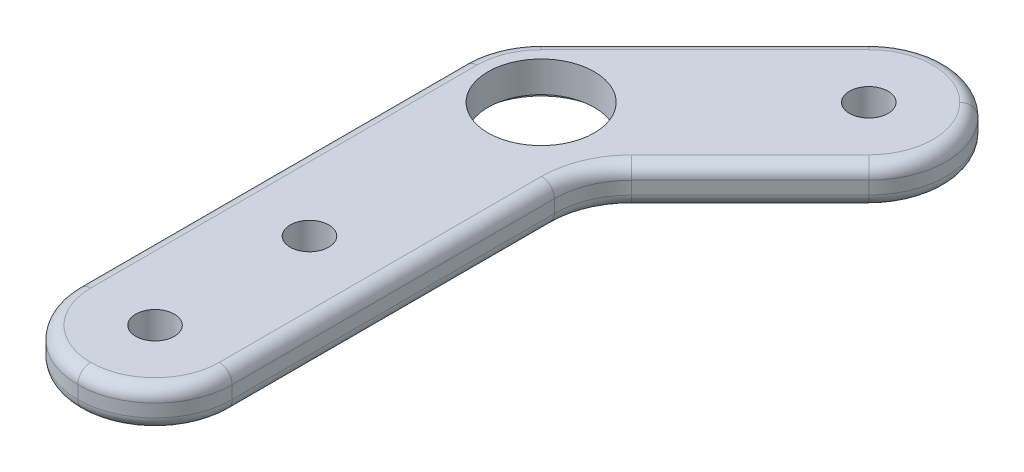
SolidWorks part; units mm, degrees
material "6061 Alloy"
ref_plane "Front Plane" through (0, 0, 0) normal (0, 0, 1) x (1, 0, 0)
ref_plane "Top Plane" through (0, 0, 0) normal (0, 1, 0) x (1, 0, 0)
ref_plane "Right Plane" through (0, 0, 0) normal (1, 0, 0) x (0, 0, -1)
sketch "Sketch1" plane through (0, 0, 0) normal (0, 1, 0) x (1, 0, 0)
  line L0 (0, 44.45) -> (0, -44.45) construction
  line L1 (-12.7, -44.45) -> (12.7, -44.45)
  line L2 (-12.7, -44.45) -> (-12.7, 31.75)
  line L3 (-12.7, 44.45) -> (12.7, 44.45) construction
  line L4 (12.7, -44.45) -> (12.7, 31.75)
  line L5 (-12.7, -44.45) -> (12.7, 44.45) construction
  line L6 (-12.7, 44.45) -> (12.7, -44.45) construction
  line L7 (0, 31.75) -> (35.921, 67.671) construction
  line L8 (8.9803, 22.7697) -> (44.9013, 58.6908)
  line L9 (44.9013, 58.6908) -> (26.9408, 76.6513)
  line L10 (26.9408, 76.6513) -> (-8.9803, 40.7303)
  line L11 (-8.9803, 40.7303) -> (8.9803, 22.7697) construction
  line L12 (12.7, 44.45) -> (12.7, 31.75) construction
  line L13 (44.9013, 58.6908) -> (44.9013, -44.45) construction
  line L14 (44.9013, -44.45) -> (12.7, -44.45) construction
  circle A0 centre (0, 31.75) radius 12.7
  circle A1 centre (0, -31.75) radius 3.175
  circle A2 centre (0, -6.35) radius 3.175
  circle A3 centre (0, 31.75) radius 8.7312
  circle A4 centre (26.9408, 58.6908) radius 3.175
  point P0 (0, 0)
  point P16 (35.921, 67.671)
  point P21 (0, 31.75)
  dimension "D4" = 12.7
  dimension "D1" = 6.35
  dimension "D7" = 38.1
  dimension "D8" = 12.7
  dimension "D9" = 17.4625
  dimension "D2" = 25.4
  dimension "D3" = 45
  dimension "D5" = 25.4
  dimension "D6" = 38.1
extrude "Boss-Extrude1" add sketch "Sketch1" along normal blind 6.35 contours A0 L2 L1 L4 L8 A2 A1 | A0 A3 | A0 L4 L8 L9 L10 A4 | A0 L8 L4 region at (-0.0256, 0, 11.0536) region at (-11.4014, 0, -36.4726) region at (11.9359, 0, -26.806) region at (21.2757, 0, -53.0842)
fillet "Fillet2" radius 12.7 5 edges at (12.7, 3.175, -26.4895) (26.9408, 3.175, -76.6513) (44.9013, 3.175, -58.6908) (-12.7, 3.175, 44.45) (12.7, 3.175, 44.45)
fillet "Fillet3" radius 2.1167 20 edges at (13.6667, 0, -26.0891) (12.7, 0, 5.2605) (8.9803, 0, 40.7303) (-8.9803, 0, 40.7303) (-12.7, 0, 0) (-11.7333, 0, -36.6101) (4.4901, 0, -54.2006) (26.9408, 0, -71.3908) (39.6408, 0, -58.6908) (13.6667, 6.35, -26.0891) (12.7, 6.35, 5.2605) (8.9803, 6.35, 40.7303) (-8.9803, 6.35, 40.7303) (-12.7, 6.35, 0) (-11.7333, 6.35, -36.6101) (4.4901, 6.35, -54.2006) (26.9408, 6.35, -71.3908) (39.6408, 6.35, -58.6908) (26.1704, 0, -39.9599) (26.1704, 6.35, -39.9599)
sketch "Sketch3" plane through (0, 0, 0) normal (0, -1, 0) x (1, 0, 0)
  circle A0 centre (0, -31.75) radius 10.2489
  dimension "D1" = 20.4978
extrude "Cut-Extrude1" cut sketch "Sketch3" against normal blind 1.27
